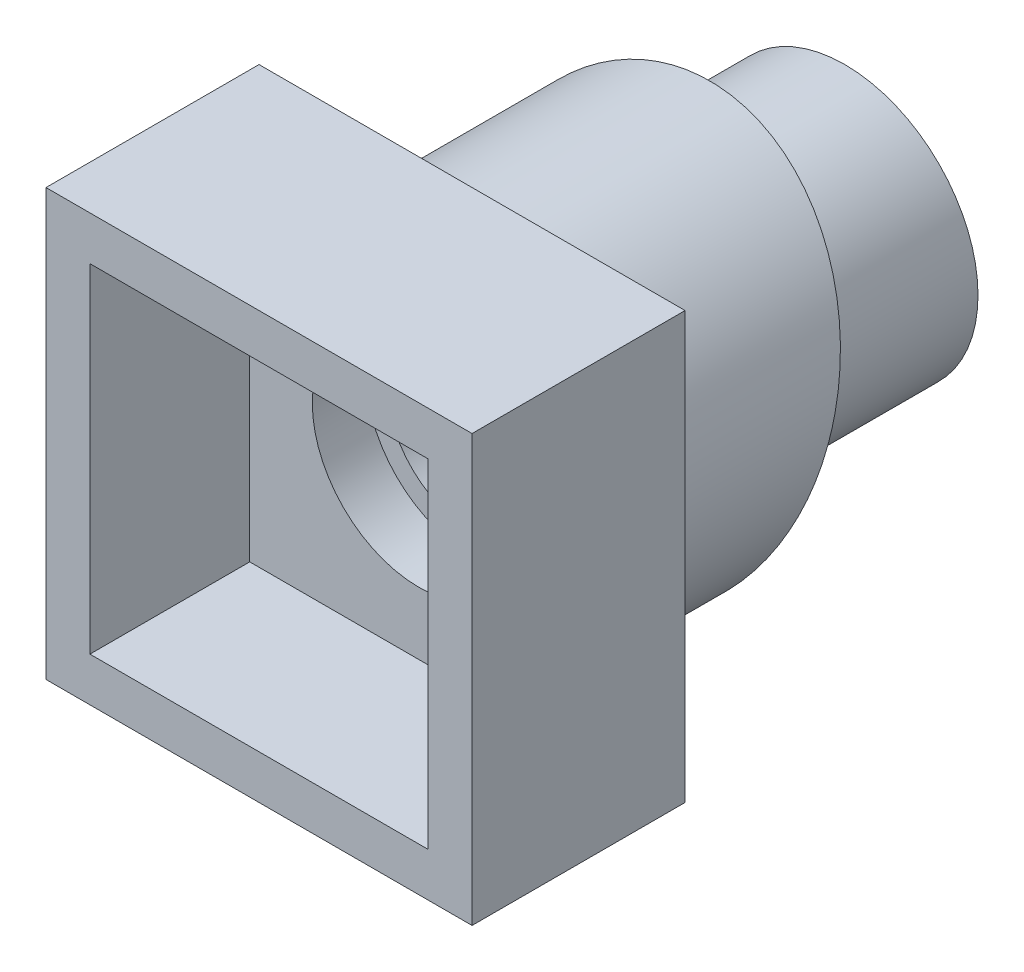
SolidWorks part; units mm, degrees
ref_plane "Alzado" through (0, 0, 0) normal (0, 0, 1) x (1, 0, 0)
ref_plane "Planta" through (0, 0, 0) normal (0, 1, 0) x (1, 0, 0)
ref_plane "Vista lateral" through (0, 0, 0) normal (1, 0, 0) x (0, 0, -1)
sketch "Croquis1" plane through (0, 0, 0) normal (0, 0, 1) x (1, 0, 0)
  circle A0 centre (0, 0) radius 2.5
  circle A1 centre (0, 0) radius 1.8
  dimension "D1" = 5
  dimension "D2" = 3.6
extrude "Saliente-Extruir1" add sketch "Croquis1" along normal blind 7
ref_axis "Eje1" through (2.75, 0, 7) along (-1, 0, 0)
ref_plane "Plano1" through (0, 2.2498, 6.1812) normal (0, -0.342, -0.9397) x (-1, 0, 0)
ref_plane "Plano3" through (0, 1.2237, 3.3621) normal (0, -0.342, -0.9397) x (-1, 0, 0)
sketch "Croquis3" plane through (0, 0, 7) normal (0, 0, 1) x (1, 0, 0)
  circle A0 centre (0, 0) radius 1.6
  circle A1 centre (0, 0) radius 3.5
  dimension "D1" = 7
extrude "Saliente-Extruir2" add sketch "Croquis3" against normal up to surface (3.1925 mm away) up to plane "Plano3"
sketch "Croquis4" plane through (0, 0, 7) normal (0, 0, 1) x (1, 0, 0)
  line L1 (4, -4) -> (-4, -4)
  line L2 (4, -4) -> (4, 4)
  line L3 (4, 4) -> (-4, 4)
  line L4 (-4, -4) -> (-4, 4)
  line L5 (4, -4) -> (-4, 4) construction
  line L6 (4, 4) -> (-4, -4) construction
  circle A0 centre (0, 0) radius 2
  point P0 (0, 0)
  dimension "D3" = 4
  dimension "D1" = 8
  dimension "D2" = 8
extrude "Saliente-Extruir3" add sketch "Croquis4" along normal blind 1
sketch "Croquis6" plane through (0, 0, 8) normal (0, 0, 1) x (1, 0, 0)
  line L1 (-3.175, -3.175) -> (3.175, -3.175)
  line L2 (-3.175, -3.175) -> (-3.175, 3.175)
  line L3 (-3.175, 3.175) -> (3.175, 3.175)
  line L4 (3.175, -3.175) -> (3.175, 3.175)
  line L5 (-3.175, -3.175) -> (3.175, 3.175) construction
  line L6 (-3.175, 3.175) -> (3.175, -3.175) construction
  line L7 (-4, -4) -> (4, -4)
  line L8 (-4, -4) -> (-4, 4)
  line L9 (-4, 4) -> (4, 4)
  line L10 (4, -4) -> (4, 4)
  line L11 (-4, -4) -> (4, 4) construction
  line L12 (-4, 4) -> (4, -4) construction
  point P0 (0, 0)
  point P6 (0, 0)
  dimension "D1" = 6.35
  dimension "D2" = 6.35
extrude "Saliente-Extruir5" add sketch "Croquis6" along normal blind 3
